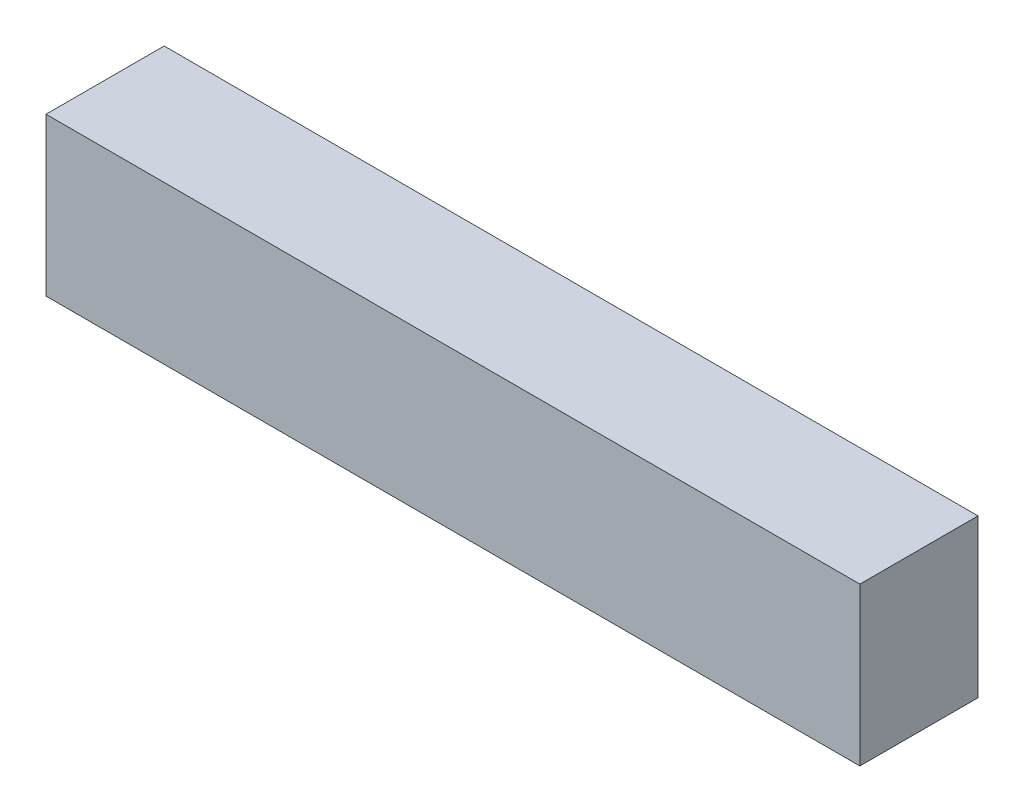
SolidWorks part; units mm, degrees
other "plenum"
ref_plane "Front Plane" through (0, 0, 0) normal (0, 0, 1) x (1, 0, 0)
ref_plane "Top Plane" through (0, 0, 0) normal (0, 1, 0) x (1, 0, 0)
ref_plane "Right Plane" through (0, 0, 0) normal (1, 0, 0) x (0, 0, -1)
other "Configuration Table"
sketch "Sketch1" plane through (0, 0, 0) normal (0, 0, 1) x (1, 0, 0)
  line L0 (300, 150) -> (4400, 150)
  line L1 (4400, 150) -> (4400, 1126.9539)
  line L2 (4400, 1126.9539) -> (3600, 1500)
  line L3 (3600, 1500) -> (300, 1500)
  line L4 (0, 1200) -> (0, 450)
  arc A0 (300, 1500) -> (0, 1200) centre (300, 1200) ccw
  arc A1 (0, 450) -> (300, 150) centre (300, 450) ccw
extrude "car_body" add sketch "Sketch1" along normal blind 900 separate body
sketch "Sketch2" plane through (0, 0, 0) normal (1, 0, 0) x (0, 0, -1)
  line L1 (10, 470) -> (-225, 470)
  line L2 (10, 470) -> (10, 820)
  line L3 (10, 820) -> (-225, 820)
  line L4 (-225, 470) -> (-225, 820)
  line L5 (10, 470) -> (-225, 820) construction
  line L6 (10, 820) -> (-225, 470) construction
extrude "grille_duct" add sketch "Sketch2" along normal blind 410 from offset 40 separate body
combine bodies "Combine1" operation type subtract main body 102 bodies to subtract 103
sketch "Sketch3" plane through (0, 0, 0) normal (1, 0, 0) x (0, 0, -1)
  line L1 (10, 100) -> (-225, 100)
  line L2 (10, 100) -> (10, 475)
  line L3 (10, 475) -> (-225, 475)
  line L4 (-225, 100) -> (-225, 475)
  line L5 (10, 100) -> (-225, 475) construction
  line L6 (10, 475) -> (-225, 100) construction
extrude "floor_exit" add sketch "Sketch3" along normal blind 150 from offset 300 separate body
combine bodies "Combine2" operation type subtract main body 104 bodies to subtract 105
sketch "Sketch4" plane through (0, 0, 0) normal (1, 0, 0) x (0, 0, -1)
  line L1 (0, 470) -> (-225, 470)
  line L2 (0, 470) -> (0, 820)
  line L3 (0, 820) -> (-225, 820)
  line L4 (-225, 470) -> (-225, 820)
  line L5 (0, 470) -> (-225, 820) construction
  line L6 (0, 820) -> (-225, 470) construction
extrude "radiator" add sketch "Sketch4" along normal blind 25 from offset 200 separate body
sketch "Sketch5" plane through (0, 0, 0) normal (1, 0, 0) x (0, 0, -1)
  line L1 (0, 470) -> (-225, 470)
  line L2 (0, 470) -> (0, 820)
  line L3 (0, 820) -> (-225, 820)
  line L4 (-225, 470) -> (-225, 820)
  line L5 (0, 470) -> (-225, 820) construction
  line L6 (0, 820) -> (-225, 470) construction
extrude "radiator_tool" add sketch "Sketch5" along normal blind 25 from offset 200 separate body
sketch "Sketch6" plane through (0, 0, 0) normal (1, 0, 0) x (0, 0, -1)
  line L1 (0, 0) -> (-4500, 0)
  line L2 (0, 0) -> (0, 6000)
  line L3 (0, 6000) -> (-4500, 6000)
  line L4 (-4500, 0) -> (-4500, 6000)
  line L5 (0, 0) -> (-4500, 6000) construction
  line L6 (0, 6000) -> (-4500, 0) construction
extrude "fluid_domain" add sketch "Sketch6" along normal blind 31000 from offset 9000 separate body offset against normal yes
combine bodies "Combine3" operation type subtract main body 109 bodies to subtract 106
combine bodies "Combine4" operation type subtract main body 110 bodies to subtract 108
